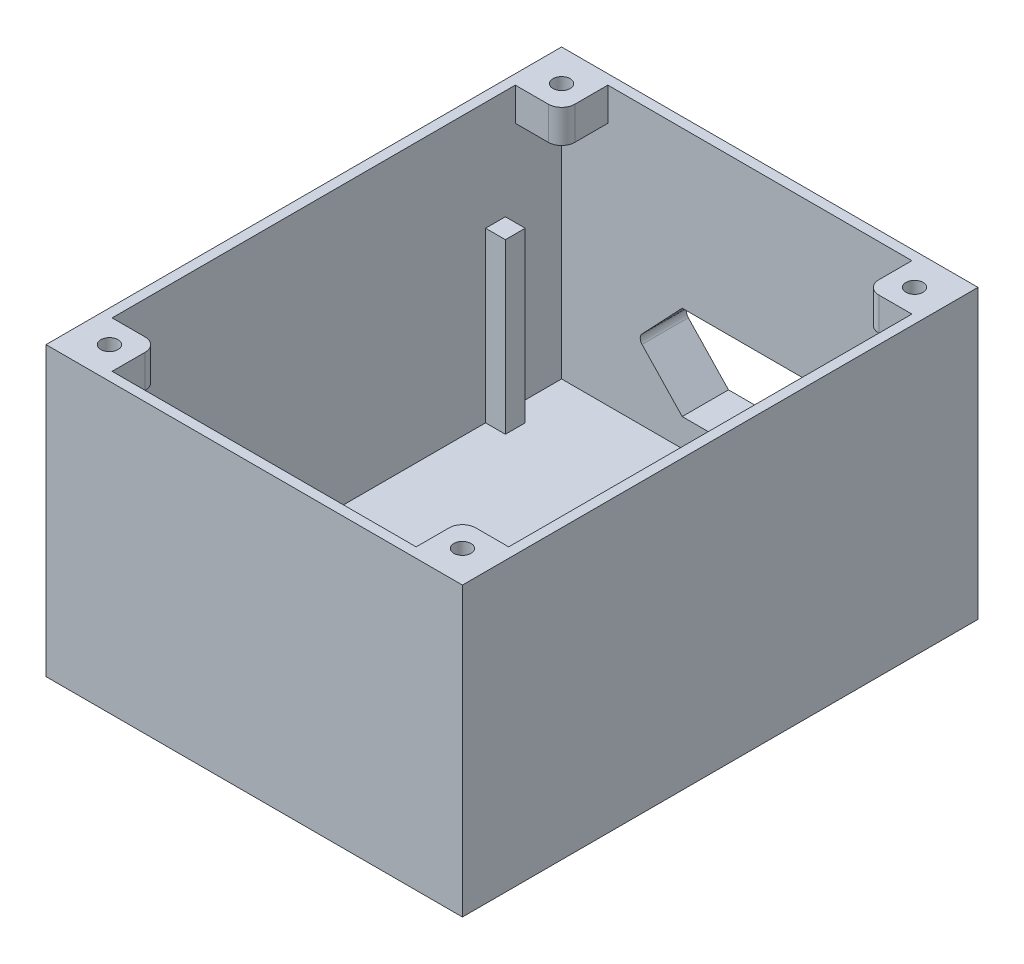
SolidWorks part; units mm, degrees
ref_plane "Plano frontal" through (0, 0, 0) normal (0, 0, 1) x (1, 0, 0)
ref_plane "Plano superior" through (0, 0, 0) normal (0, 1, 0) x (1, 0, 0)
ref_plane "Plano direito" through (0, 0, 0) normal (1, 0, 0) x (0, 0, -1)
sketch "Esboço1" plane through (0, 0, 0) normal (0, 0, 1) x (1, 0, 0)
  line L0 (11.5224, 11.3) -> (30, 11.3) construction
  line L1 (0, 0) -> (60, 0)
  line L2 (0, 0) -> (0, 42)
  line L3 (0, 42) -> (60, 42)
  line L4 (60, 0) -> (60, 42)
  line L5 (41.75, 18.4) -> (18.25, 18.4)
  line L6 (18.25, 18.4) -> (12.1741, 11.9878)
  line L7 (12.1741, 10.6122) -> (18.25, 4.2)
  line L8 (18.25, 4.2) -> (41.75, 4.2)
  line L9 (30, 18.4) -> (30, 4.2) construction
  line L10 (47.8259, 10.6122) -> (41.75, 4.2)
  line L11 (41.75, 18.4) -> (47.8259, 11.9878)
  line L12 (-1.5, 43.5) -> (61.5, 43.5)
  line L13 (61.5, -1.5) -> (61.5, 43.5)
  line L14 (-1.5, -1.5) -> (61.5, -1.5)
  line L15 (-1.5, -1.5) -> (-1.5, 43.5)
  line L16 (42.6101, 20.4) -> (49.2777, 13.3634)
  line L17 (49.2777, 9.2366) -> (42.6101, 2.2)
  line L18 (17.3899, 2.2) -> (42.6101, 2.2)
  line L19 (10.7223, 9.2366) -> (17.3899, 2.2)
  line L20 (17.3899, 20.4) -> (10.7223, 13.3634)
  line L21 (42.6101, 20.4) -> (17.3899, 20.4)
  arc A0 (47.8259, 10.6122) -> (47.8259, 11.9878) centre (47.1, 11.3) ccw
  arc A1 (12.1741, 11.9878) -> (12.1741, 10.6122) centre (12.9, 11.3) ccw
  arc A2 (49.2777, 9.2366) -> (49.2777, 13.3634) centre (47.1, 11.3) ccw
  arc A3 (10.7223, 13.3634) -> (10.7223, 9.2366) centre (12.9, 11.3) ccw
  point P5 (30, 0)
  point P19 (48.4776, 11.3)
  point P23 (11.9, 11.3)
  point P24 (48.1, 11.3)
  dimension "D4" = 1
  dimension "D1" = 14.2
  dimension "D2" = 36.2
  dimension "D3" = 23.5
  dimension "D5" = 60
  dimension "D6" = 42
  dimension "D7" = 4.2
  dimension "D8" = 1.5
  dimension "D9" = 2
extrude "Ressalto-extrusão2" add sketch "Esboço1" along normal blind 1.5 contours L15 L14 L13 L12 L4 L1 L2 L3 | L1 L4 L3 L2 A1 L6 L5 L11 A0 L10 L8 L7 | L1 L4 L3 L2 A3 L20 L21 L16 A2 L17 L18 L19 region at (30, 24.1149, 0) region at (30, 42.7258, 0) region at (45.6236, 16.5782, 0)
extrude "Ressalto-extrusão3" add sketch "Esboço1<3>" along normal blind 75 from surface contours L15 L14 L13 L12 L4 L1 L2 L3 region at (30, 42.7258, 0) starting at face at (30, 21, 1.5)
sketch "Esboço1<3>" plane through (0, 0, 0) normal (0, 0, 1) x (1, 0, 0) same geometry as "Esboço1"
sketch "Esboço2" plane through (0, 0, 0) normal (0, 1, 0) x (1, 0, 0)
  line L0 (30, -54.8) -> (30, -76.5) construction
  line L1 (41.75, -54.8) -> (48.6644, -62.2482)
  line L2 (48.6644, -69.0518) -> (41.75, -76.5)
  line L3 (61.5, -76.5) -> (-1.5, -76.5) construction
  line L4 (41.75, -54.8) -> (18.25, -54.8)
  line L5 (18.25, -54.8) -> (11.3356, -62.2482)
  line L6 (11.3356, -69.0518) -> (18.25, -76.5)
  line L7 (18.25, -76.5) -> (41.75, -76.5)
  line L8 (42.4042, -53.3) -> (49.7637, -61.2277)
  line L9 (49.7637, -70.0723) -> (42.4042, -78)
  line L10 (17.5958, -78) -> (42.4042, -78)
  line L11 (10.2363, -70.0723) -> (17.5958, -78)
  line L12 (17.5958, -53.3) -> (10.2363, -61.2277)
  line L13 (42.4042, -53.3) -> (17.5958, -53.3)
  line L14 (51.5, -65.65) -> (50, -65.65)
  line L15 (10, -65.65) -> (8.5, -65.65)
  line L16 (47.5651, -68.0312) -> (41.0958, -75)
  line L17 (18.9042, -75) -> (41.0958, -75)
  line L18 (12.4349, -68.0312) -> (18.9042, -75)
  line L19 (18.9042, -56.3) -> (12.4349, -63.2688)
  line L20 (41.0958, -56.3) -> (18.9042, -56.3)
  line L21 (41.0958, -56.3) -> (47.5651, -63.2688)
  arc A0 (11.3356, -62.2482) -> (11.3356, -69.0518) centre (15, -65.65) ccw
  arc A1 (48.6644, -62.2482) -> (48.6644, -69.0518) centre (45, -65.65) cw
  arc A2 (49.7637, -61.2277) -> (49.7637, -70.0723) centre (45, -65.65) cw
  arc A3 (10.2363, -61.2277) -> (10.2363, -70.0723) centre (15, -65.65) ccw
  arc A4 (12.4349, -63.2688) -> (12.4349, -68.0312) centre (15, -65.65) ccw
  arc A5 (47.5651, -63.2688) -> (47.5651, -68.0312) centre (45, -65.65) cw
  point P4 (30, -76.5)
  point P8 (30, -65.65)
  point P15 (8.1776, -65.65)
  point P18 (51.8224, -65.65)
  point P19 (50, -65.65)
  point P20 (10, -65.65)
  line M12 (0, -76.5) -> (60, -76.5)
  dimension "D1" = 5
  dimension "D2" = 40
  dimension "D3" = 21.7
  dimension "D4" = 23.5
  dimension "D5" = 1.5
  dimension "D6" = 1.5
extrude "Ressalto-extrusão4" add sketch "Esboço2" along normal blind 15 contours L12 A3 L15 A0 L5 L4 L1 A1 L14 A2 L8 L13 | L15 A3 L11 L6 A0 M12 | A2 L14 A1 L2 L9 M12 region at (30, 0, 54.3526) region at (47.3129, 0, 71.3654) region at (12.6871, 0, 71.3654)
extrude "Corte-extrusão1" cut sketch "Esboço2<3>" against normal blind 27 contours L20 L0 L17 L16 A5 L21 | L0 L20 L19 A4 L18 L17 region at (37.8375, 0, 65.65) region at (22.1625, 0, 65.65)
sketch "Esboço2<3>" plane through (0, 0, 0) normal (0, 1, 0) x (1, 0, 0) same geometry as "Esboço2"
sketch "Esboço4" plane through (0, 0, 76.5) normal (0, 0, 1) x (1, 0, 0)
  line L1 (-1.5, 43.5) -> (61.5, 43.5)
  line L2 (-1.5, 43.5) -> (-1.5, -1.5)
  line L3 (-1.5, -1.5) -> (61.5, -1.5)
  line L4 (61.5, 43.5) -> (61.5, -1.5)
extrude "Ressalto-extrusão6" add sketch "Esboço4" along normal blind 1.5
sketch "Esboço5" plane through (0, 0, 78) normal (0, 0, 1) x (1, 0, 0)
  line L0 (61.5, -1.5) -> (61.5, 43.5) construction
  line L1 (-1.5, 43.5) -> (61.5, 43.5)
  line L2 (-1.5, 43.5) -> (-1.5, 42)
  line L3 (-1.5, 42) -> (61.5, 42)
  line L4 (61.5, 43.5) -> (61.5, 42)
  dimension "D1" = 1.5
extrude "Corte-extrusão2" cut sketch "Esboço5" against normal through all
sketch "Esboço6" plane through (0, 0, 0) normal (0, 1, 0) x (1, 0, 0)
  line L0 (60, -76.5) -> (60, -1.5) construction
  line L2 (60, -1.5) -> (0, -1.5) construction
  line L3 (60, -1.5) -> (60, -8.5)
  line L4 (60, -76.5) -> (60, -1.5) construction
  line L5 (60, -8.5) -> (55, -8.5)
  line L6 (53, -6.5) -> (53, -1.5)
  line L7 (60, -1.5) -> (0, -1.5) construction
  line L8 (53, -1.5) -> (60, -1.5)
  circle A0 centre (56.7, -4.8) radius 1.3
  arc A1 (55, -8.5) -> (53, -6.5) centre (55, -6.5) cw
  dimension "D1" = 2.6
  dimension "D6" = 2
  dimension "D2" = 3.3
  dimension "D3" = 3.3
  dimension "D4" = 7
  dimension "D5" = 7
extrude "Ressalto-extrusão7" add sketch "Esboço6" against normal blind 5 from surface starting at face at (30, 42, 39)
ref_plane "Plano1" through (0, 0, 39) normal (0, 0, 1) x (1, 0, 0)
ref_plane "Plano2" through (30, 0, 0) normal (-1, 0, 0) x (0, 0, 1)
mirror "Espelhar1" about plane through (0, 0, 39) normal (0, 0, 1) of "Ressalto-extrusão7"
mirror "Espelhar2" about plane through (30, 0, 0) normal (-1, 0, 0) of "Espelhar1"
extrude "Ressalto-extrusão8" add sketch "Esboço1<4>" against normal blind 5.5 contours L20 A3 L19 L18 L17 A2 L16 L21 A1 L6 L5 L11 A0 L10 L8 L7 region at (45.6236, 16.5782, 0)
sketch "Esboço1<4>" plane through (0, 0, 0) normal (0, 0, 1) x (1, 0, 0) same geometry as "Esboço1"
sketch "Esboço7" plane through (0, 0, 0) normal (0, 1, 0) x (1, 0, 0)
  line L0 (60, -76.5) -> (60, -1.5) construction
  line L1 (60, -10) -> (57, -10)
  line L2 (60, -10) -> (60, -13)
  line L3 (60, -13) -> (57, -13)
  line L4 (57, -10) -> (57, -13)
  line L5 (60, -7) -> (57.1201, -7) construction
  line L6 (60, -1.5) -> (0, -1.5) construction
  dimension "D1" = 5.5
  dimension "D2" = 3
  dimension "D3" = 3
  dimension "D4" = 3
extrude "Ressalto-extrusão9" add sketch "Esboço7" along normal blind 25.5
mirror "Espelhar3" about plane through (30, 0, 0) normal (-1, 0, 0) of "Ressalto-extrusão9"
